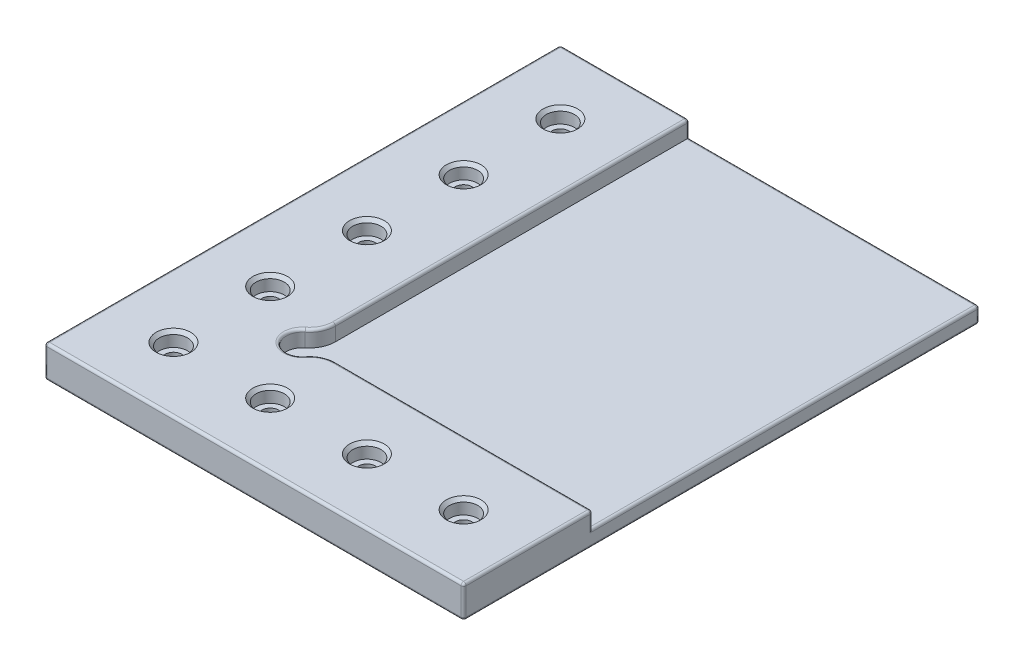
SolidWorks part; units mm, degrees
ref_plane "Front Plane" through (0, 0, 0) normal (0, 0, 1) x (1, 0, 0)
ref_plane "Top Plane" through (0, 0, 0) normal (0, 1, 0) x (1, 0, 0)
ref_plane "Right Plane" through (0, 0, 0) normal (1, 0, 0) x (0, 0, -1)
sketch "Base Plate" plane through (0, 0, 0) normal (0, 1, 0) x (1, 0, 0)
  line L1 (-41.275, 50.8) -> (41.275, 50.8)
  line L2 (-41.275, 50.8) -> (-41.275, -50.8)
  line L3 (-41.275, -50.8) -> (41.275, -50.8)
  line L4 (41.275, 50.8) -> (41.275, -50.8)
  line L5 (-41.275, 50.8) -> (41.275, -50.8) construction
  line L6 (-41.275, -50.8) -> (41.275, 50.8) construction
  point P0 (0, 0)
extrude "Main Body" add sketch "Base Plate" along normal blind 6.35
sketch "Hole Positions" plane through (0, 6.35, 0) normal (0, 1, 0) x (1, 0, 0)
  point P0 (-28.575, -38.1)
  point P2 (-9.525, -38.1)
  point P4 (9.525, -38.1)
  point P6 (28.575, -38.1)
  point P8 (-28.575, -19.05)
  point P10 (-28.575, 0)
  point P12 (-28.575, 19.05)
  point P14 (-28.575, 38.1)
hole_wizard "Mounting Holes (CBORE) " positions "Hole Positions" profile "Hole Profile" counterbore size "#4" standard "ANSI Inch" end condition through all
sketch "Hole Profile" plane through (-28.575, 6.35, 38.1) normal (1, 0, 0) x (0, 0, 1)
  line L0 (0, 0) -> (0, 6.35)
  line L1 (0, 6.35) -> (1.6319, 6.35)
  line L3 (1.6319, 6.35) -> (1.632, 2.8448)
  line L4 (2.7788, 2.8448) -> (1.632, 2.8448)
  line L5 (2.7788, 2.8448) -> (2.7788, 0.635)
  line L6 (2.7788, 0.635) -> (3.4138, 0)
  line L7 (3.4138, 0) -> (0, 0)
  line L8 (-2.7788, 0.635) -> (-3.4138, 0) construction
  line L11 (0, -6.35) -> (0, 107.95) construction
  dimension "Thru Hole Dia." = 3.2639
  dimension "Thru Hole Depth" = 6.35
  dimension "C'Bore Dia." = 5.5575
  dimension "C'Bore Depth" = 2.8448
  dimension "Near C'Sink Dia." = 6.8275
  dimension "Near C'Sink Angle" = 90
sketch "L-Area Exclusion  " plane through (0, 6.35, 0) normal (0, 1, 0) x (1, 0, 0)
  line L0 (41.275, 50.8) -> (-41.275, 50.8) construction
  line L1 (41.275, 50.8) -> (-15.875, 50.8)
  line L2 (41.275, 50.8) -> (41.275, -25.4)
  line L3 (41.275, -25.4) -> (-15.875, -25.4)
  line L4 (-15.875, 50.8) -> (-15.875, -25.4)
  line L5 (-41.275, 50.8) -> (-41.275, -50.8) construction
  line L6 (41.275, -50.8) -> (41.275, 50.8) construction
  line L7 (-41.275, -50.8) -> (41.275, -50.8) construction
  dimension "D1" = 0
  dimension "D2" = 25.4
  dimension "D3" = 0
  dimension "D4" = 25.4
extrude "L-Area Step Cut " cut sketch "L-Area Exclusion  " against normal blind 3.175
sketch "Relief Circle Sketch" plane through (0, 6.35, 0) normal (0, 1, 0) x (1, 0, 0)
  circle A0 centre (-15.875, -25.4) radius 3.175
  dimension "D1" = 6.35
extrude "Substrate Relief Pocket" cut sketch "Relief Circle Sketch" against normal blind 3.175
fillet "Relief Circle Corner Blend" radius 5.08 2 edges at (-12.7, 4.7625, 25.4) (-15.875, 4.7625, 22.225)
fillet "Outer Edge Softening" radius 0.508 21 edges at (15.9534, 6.35, 25.4) (-11.5959, 6.35, 25.9145) (-18.1201, 6.35, 27.6451) (-16.3895, 6.35, 21.1209) (41.275, 6.35, 38.1) (-41.275, 0, 0) (0, 0, 50.8) (0, 6.35, 50.8) (-15.875, 6.35, -15.9534) (-41.275, 6.35, 0) (0, 0, -50.8) (-15.875, 4.7625, -50.8) (-28.575, 6.35, -50.8) (12.7, 3.175, -50.8) (41.275, 0, 0) (41.275, 3.175, -12.7) (41.275, 4.7625, 25.4) (41.275, 3.175, 50.8) (41.275, 1.5875, -50.8) (-41.275, 3.175, -50.8) (-41.275, 3.175, 50.8)
